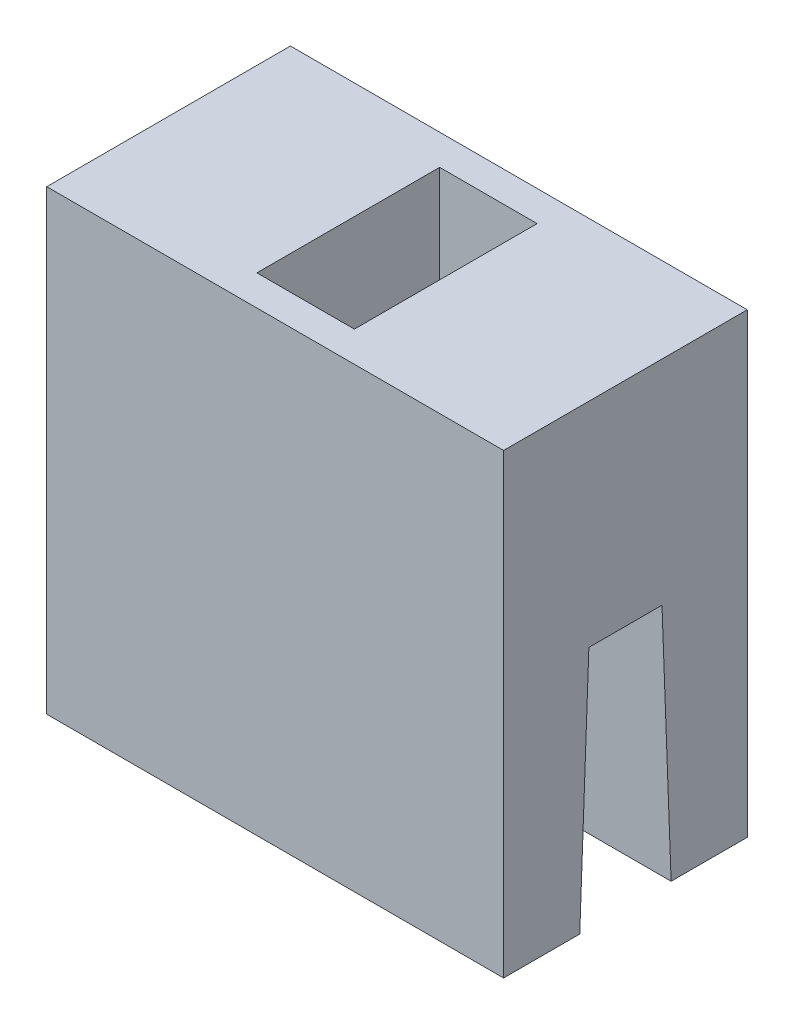
SolidWorks part; units mm, degrees
ref_plane "Front Plane" through (0, 0, 0) normal (0, 0, 1) x (1, 0, 0)
ref_plane "Top Plane" through (0, 0, 0) normal (0, 1, 0) x (1, 0, 0)
ref_plane "Right Plane" through (0, 0, 0) normal (1, 0, 0) x (0, 0, -1)
sketch "Sketch1" plane through (0, 0, 0) normal (1, 0, 0) x (0, 0, -1)
  line L0 (-1.5, 0) -> (-1.2, 8)
  line L1 (-1.2, 8) -> (1.2, 8)
  line L2 (1.2, 8) -> (1.5, 0)
  line L3 (1.5, 0) -> (4, 0)
  line L4 (4, 0) -> (4, 15)
  line L5 (4, 15) -> (-4, 15)
  line L6 (-4, 15) -> (-4, 0)
  line L7 (-4, 0) -> (-1.5, 0)
  point P9 (0, 8)
  point P10 (0, 15)
  point P11 (0, 0)
  point P12 (-1.2286, 3.1016)
  dimension "D1" = 0.3
  dimension "D2" = 3
  dimension "D3" = 8
  dimension "D4" = 7
  dimension "D5" = 8
extrude "Boss-Extrude1" add sketch "Sketch1" along normal mid plane 15
sketch "Sketch2" plane through (0, 15, 0) normal (0, 1, 0) x (1, 0, 0)
  line L0 (7.5, 4) -> (-7.5, 4) construction
  line L1 (1.6, 3) -> (-1.6, 3)
  line L2 (1.6, 3) -> (1.6, -3)
  line L3 (1.6, -3) -> (-1.6, -3)
  line L4 (-1.6, 3) -> (-1.6, -3)
  point P4 (0, 3)
  point P5 (1.6, 0)
  point P6 (0, 0)
  point P8 (6.2061, 0.387)
  dimension "D1" = 3.2
  dimension "D2" = 1
extrude "Cut-Extrude1" cut sketch "Sketch2" against normal blind 5
fillet "Fillet1" radius 1.5 2 edges at (-1.6, 10, 0) (1.6, 10, 0)
